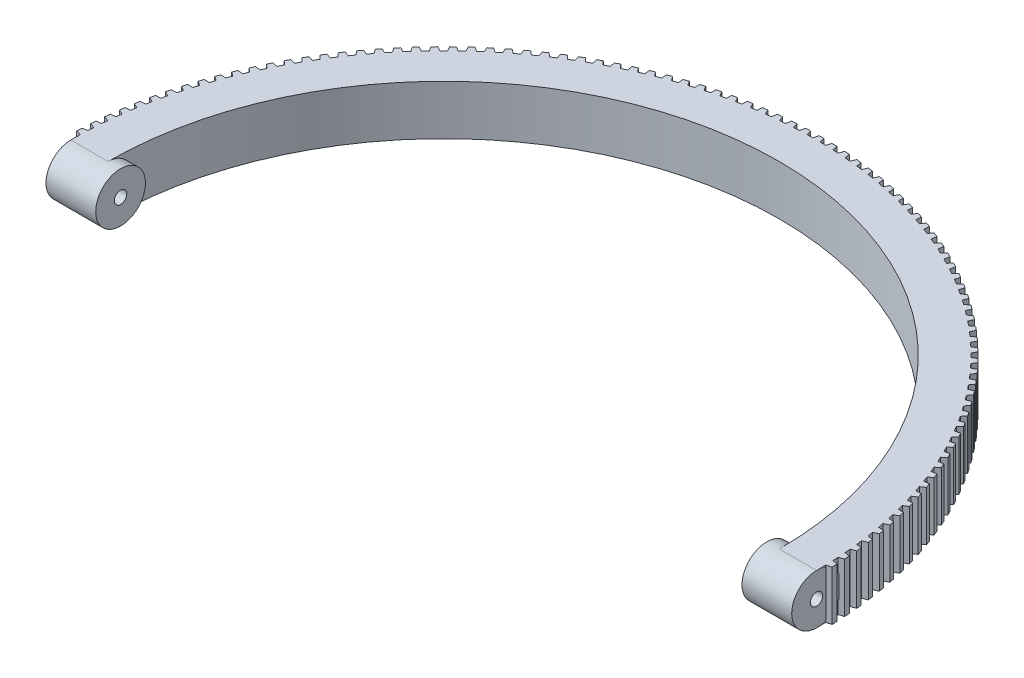
SolidWorks part; units mm, degrees
ref_plane "Front Plane" through (0, 0, 0) normal (0, 0, 1) x (1, 0, 0)
ref_plane "Top Plane" through (0, 0, 0) normal (0, 1, 0) x (1, 0, 0)
ref_plane "Right Plane" through (0, 0, 0) normal (1, 0, 0) x (0, 0, -1)
sketch "Sketch1" plane through (0, 0, 0) normal (0, 1, 0) x (1, 0, 0)
  line L0 (-150, 0) -> (0, 0)
  line L1 (0, 0) -> (150, 0)
  line L2 (-150, 0) -> (-157.0075, 0)
  circle A0 centre (0, 0) radius 150
  circle A1 centre (0, 0) radius 135
  dimension "D1" = 300
  dimension "D2" = 270
extrude "Boss-Extrude2" add sketch "Sketch1" along normal blind 20 contours A1 L1 A0 L0 region at (0, 0, -146.6459)
sketch "Sketch2" plane through (0, 20, 0) normal (0, 1, 0) x (1, 0, 0)
  line L0 (0, 150) -> (0, 152) construction
  line L1 (0, 152) -> (-1, 152)
  line L2 (-1, 152) -> (1, 152)
  line L3 (-1, 152) -> (-2, 148)
  line L4 (-2, 148) -> (2, 148)
  line L5 (2, 148) -> (1, 152)
  line L6 (0, 150) -> (0, 148) construction
  arc A0 (150, 0) -> (-150, 0) centre (0, 0) ccw construction
  arc M9 (150, 0) -> (-150, 0) centre (0, 0) ccw
  dimension "D1" = 2
  dimension "D2" = 1
  dimension "D3" = 4
  dimension "D4" = 2
  dimension "D5" = 1
  dimension "D6" = 2
  dimension "D7" = 2
extrude "Boss-Extrude3" add sketch "Sketch2" against normal blind 20 contours L5 L2 L1 L3 M9 region at (0, 20, -150.9319)
pattern_circular "CirPattern1" count 45 every 2 about axis through (0, 20, 0) along (0, 1, 0) of "Boss-Extrude3"
mirror "Mirror1" about plane through (0, 0, 0) normal (1, 0, 0) of "CirPattern1"
ref_plane "Plane1" through (150, 0, 0) normal (1, 0, 0) x (0, 0, -1)
sketch "Sketch3" plane through (150, 0, 0) normal (1, 0, 0) x (0, 0, -1)
  line L0 (0, 20) -> (0, 0) construction
  circle A0 centre (0, 10) radius 10
  dimension "D1" = 20
extrude "Boss-Extrude4" add sketch "Sketch3" against normal blind 20
mirror "Mirror2" about plane through (0, 0, 0) normal (1, 0, 0) of "Boss-Extrude4"
sketch "Sketch5" plane through (150, 0, 0) normal (1, 0, 0) x (0, 0, -1)
  circle A0 centre (0, 10) radius 2.5
  dimension "D2" = 5
  dimension "D1" = 10
  dimension "D3" = 10
extrude "Cut-Extrude1" cut sketch "Sketch5" against normal blind 20
mirror "Mirror3" about plane through (0, 0, 0) normal (1, 0, 0) of "Cut-Extrude1"
ref_plane "Plane2" through (0, 0, -150) normal (0, 0, 1) x (1, 0, 0)
